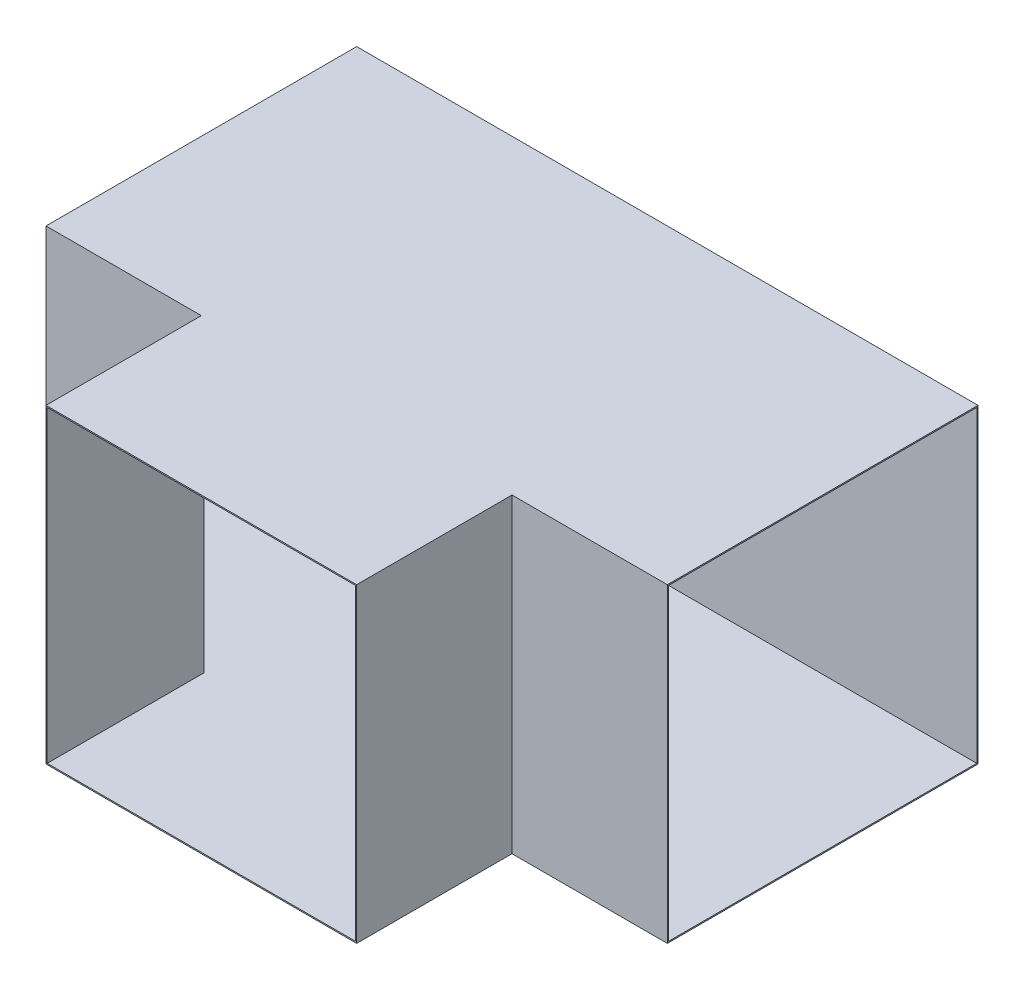
SolidWorks part; units mm, degrees
material "Plain Carbon Steel"
ref_plane "Front Plane" through (0, 0, 0) normal (0, 0, 1) x (1, 0, 0)
ref_plane "Top Plane" through (0, 0, 0) normal (0, 1, 0) x (1, 0, 0)
ref_plane "Right Plane" through (0, 0, 0) normal (1, 0, 0) x (0, 0, -1)
sketch "Sketch1" plane through (0, 0, 0) normal (1, 0, 0) x (0, 0, -1)
  line L0 (-250, 250) -> (250, -250) construction
  line L1 (-250, 250) -> (250, 250)
  line L2 (-250, 250) -> (-250, -250)
  line L3 (-250, -250) -> (250, -250)
  line L4 (250, 250) -> (250, -250)
  line L5 (-250, -250) -> (250, 250) construction
  dimension "Width" = 500
  dimension "Height" = 500
extrude "Extrude-Thin1" add sketch "Sketch1" along normal mid plane 1000 thin thin type one direction reverse wall 2
sketch "Sketch2" plane through (0, -250, 250) normal (0, 0, -1) x (1, 0, 0)
  line L1 (-250, 0) -> (250, 0)
  line L2 (-250, 0) -> (-250, -500)
  line L3 (-250, -500) -> (250, -500)
  line L4 (250, 0) -> (250, -500)
  line L6 (-250, 0) -> (250, -500) construction
  line L7 (-250, -500) -> (250, 0) construction
  dimension "Width" = 500
  dimension "Height" = 500
extrude "Extrude-Thin2" add sketch "Sketch2" against normal blind 250 thin thin type one direction reverse wall 2
sketch "Sketch3" plane through (0, -750, 500) normal (0, 0, -1) x (1, 0, 0)
  line L0 (-248, -502) -> (-248, -998) construction
  line L1 (-248, -998) -> (248, -998) construction
  line L2 (248, -998) -> (248, -502) construction
  line L3 (248, -502) -> (-248, -502) construction
  line L4 (-248, -502) -> (-248, -998)
  line L5 (-248, -998) -> (248, -998)
  line L6 (248, -998) -> (248, -502)
  line L7 (248, -502) -> (-248, -502)
extrude "Cut-Extrude1" cut sketch "Sketch3" along normal up to next
sketch "Sketch4" plane through (0, 0, 0) normal (0, 1, 0) x (1, 0, 0)
  line L0 (248, -500) -> (-248, -500) construction
  line L3 (500, -248) -> (500, 248) construction
  line L4 (-500, -248) -> (-500, 248) construction
  point P0 (500, 0)
  point P1 (-500, 0)
  point P2 (0, -500)
  point P3 (0, 0)
other "CPoint1" parameters "Diameter"=10, "StubLength"=500
ref_axis "Axis1" through (510, 0, 0) along (-1, 0, 0)
other "CPoint2" parameters "Diameter"=10, "StubLength"=500
ref_axis "Axis2" through (-510, 0, 0) along (1, 0, 0)
other "CPoint3" parameters "Diameter"=10, "StubLength"=500
ref_axis "Axis3" through (0, 0, 510) along (0, 0, -1)
other "RPoint1"
equation "\"Thickness@Extrude-Thin2\" = \"Thickness@Extrude-Thin1\""
equation "\"D1@Extrude-Thin1\"=2 * \"Width@Sketch1\""
equation "\"D1@Extrude-Thin2\"=0.5 * \"Width@Sketch1\""
